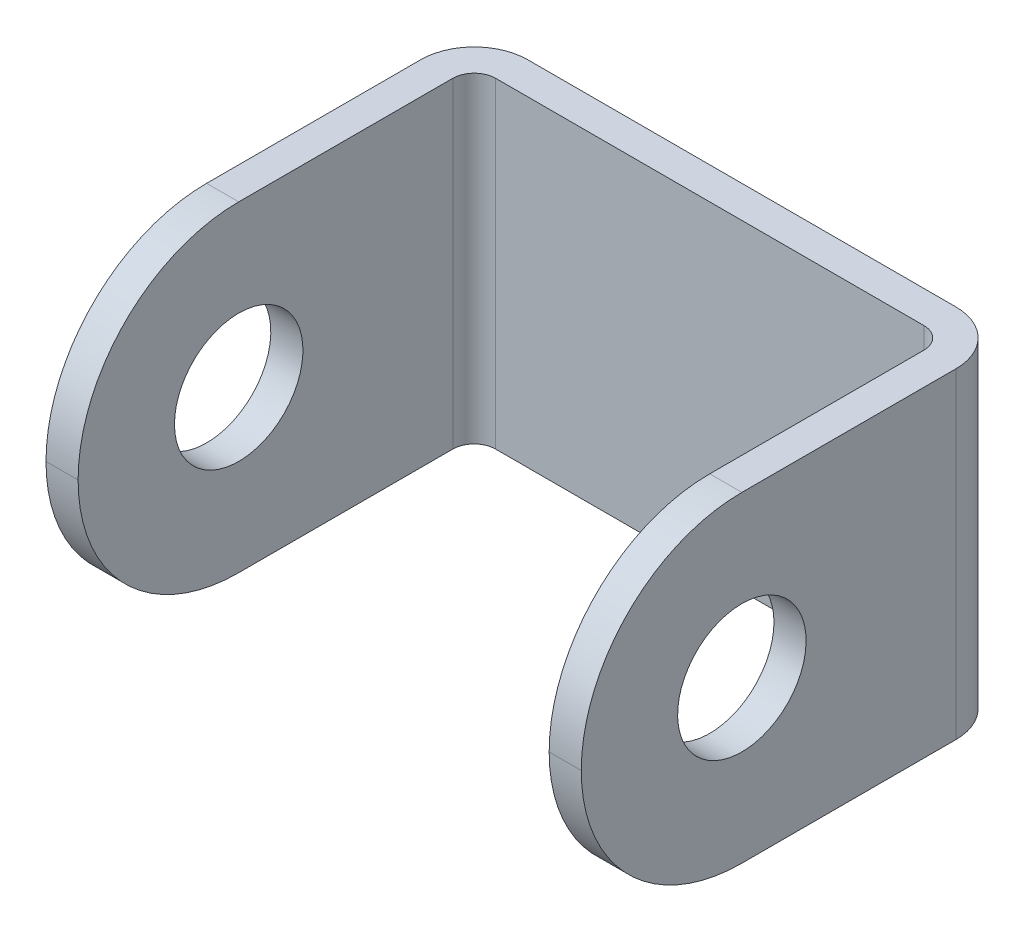
SolidWorks part; units mm, degrees
ref_plane "Přední rovina" through (0, 0, 0) normal (0, 0, 1) x (1, 0, 0)
ref_plane "Horní rovina" through (0, 0, 0) normal (0, 1, 0) x (1, 0, 0)
ref_plane "Pravá rovina" through (0, 0, 0) normal (1, 0, 0) x (0, 0, -1)
sketch "Skica1" plane through (0, 0, 0) normal (0, 0, 1) x (1, 0, 0)
  line L0 (0, 22.8047) -> (0, -25.6339) construction
  line L1 (-25, 15) -> (25, 15)
  line L2 (-25, 15) -> (-25, -15)
  line L3 (-25, -15) -> (25, -15)
  line L4 (25, 15) -> (25, -15)
  line L5 (29.0912, 0) -> (-25.1344, 0) construction
  dimension "D1" = 30
  dimension "D2" = 50
extrude "Přidat vysunutím1" add sketch "Skica1" along normal blind 40
fillet "Zaoblit1" radius 15 2 edges at (0, -15, 40) (0, 15, 40)
sketch "Skica2" plane through (0, 0, 0) normal (0, 1, 0) x (1, 0, 0)
  line L0 (0, 8.9112) -> (0, -44.0298) construction
  line L1 (-22, -53) -> (22, -53)
  line L2 (-22, -53) -> (-22, -3)
  line L3 (-22, -3) -> (22, -3)
  line L4 (22, -53) -> (22, -3)
  line L5 (25, 0) -> (-25, 0) construction
  dimension "D1" = 3
  dimension "D2" = 44
  dimension "D3" = 50
extrude "Odebrat vysunutím1" cut sketch "Skica2" against normal through all and the other way through all
fillet "Zaoblit2" radius 2 2 edges at (22, 0, 3) (-22, 0, 3)
fillet "Zaoblit3" radius 5 2 edges at (25, 0, 0) (-25, 0, 0)
sketch "Skica3" plane through (25, 0, 0) normal (1, 0, 0) x (0, 0, -1)
  circle A0 centre (-25, 0) radius 6
  dimension "D1" = 12
extrude "Odebrat vysunutím2" cut sketch "Skica3" against normal through all
